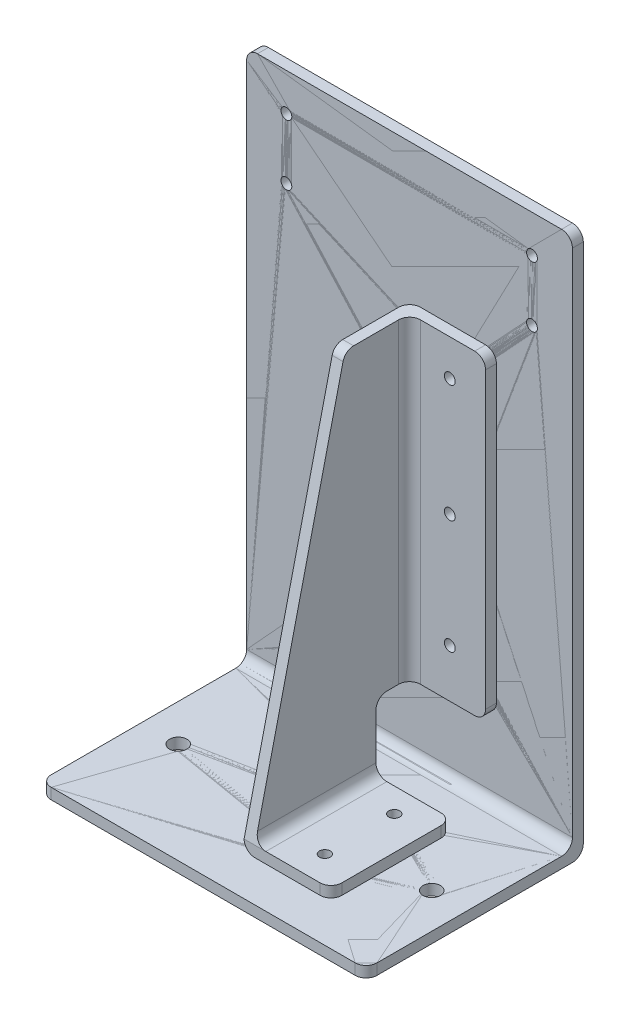
SolidWorks part; units mm, degrees
note: The reader was unsure of these and kept them because the rebuilt part matched: shared geometry of "Sketch2<3>".
ref_plane "Front Plane" through (0, 0, 0) normal (0, 0, 1) x (1, 0, 0)
ref_plane "Top Plane" through (0, 0, 0) normal (0, 1, 0) x (1, 0, 0)
ref_plane "Right Plane" through (0, 0, 0) normal (1, 0, 0) x (0, 0, -1)
sketch "Sketch1" plane through (0, 0, 0) normal (1, 0, 0) x (0, 0, -1)
  line L0 (-200, 0) -> (0, 0)
  line L1 (0, 0) -> (0, 500)
  line L2 (-200, 10) -> (-10, 10)
  line L3 (-10, 10) -> (-10, 500)
  line L4 (-200, 0) -> (-200, 10)
  line L5 (0, 500) -> (-10, 500)
  dimension "D1" = 500
  dimension "D2" = 200
  dimension "D3" = 10
extrude "Boss-Extrude1" add sketch "Sketch1" against normal blind 300 contours L1 L5 L3 L2 L4 L0
sketch "Sketch2" plane through (0, 0, 0) normal (1, 0, 0) x (0, 0, -1)
  line L0 (-10, 372.8517) -> (-79.4391, 372.8517)
  line L1 (-10, 10) -> (-10, 500) construction
  line L2 (-79.4391, 372.8517) -> (-162.346, 20)
  line L3 (-162.346, 20) -> (-162.346, 10)
  line L4 (-200, 10) -> (-10, 10) construction
  line L5 (-162.346, 10) -> (-50.9191, 10)
  line L6 (-50.9191, 10) -> (-50.9191, 82.1965)
  line L7 (-50.9191, 82.1965) -> (-10, 82.1965)
  line L8 (-10, 82.1965) -> (-10, 372.8517)
  line L9 (-162.346, 20) -> (-50.9191, 20)
  line L10 (-20, 82.1965) -> (-20, 372.8517)
  line L11 (-162.346, 10) -> (-162.346, 20)
  line L12 (-50.9191, 10) -> (-50.9191, 20)
  line L13 (-10, 82.1965) -> (-20, 82.1965)
  line L14 (-10, 372.8517) -> (-20, 372.8517)
  dimension "D1" = 10
  dimension "D2" = 10
extrude "Boss-Extrude2" add sketch "Sketch2" against normal blind 10 from offset 140 separate body contours L7 L10 L0 L2 L9 L6 offset against normal yes
extrude "Boss-Extrude3" add sketch "Sketch2<3>" along normal blind 80 from offset 150 contours L9 L3 L5 L6 | L10 L7 L8 L0 offset against normal yes
sketch "Sketch2<3>" plane through (0, 0, 0) normal (1, 0, 0) x (0, 0, -1) same geometry as "Sketch2"
fillet "Fillet1" radius 10 6 edges at (-300, 5, 200) (0, 5, 200) (-300, 500, 5) (0, 500, 5) (-150, 0, 0) (-150, 10, 10)
fillet "Fillet2" radius 10 10 edges at (-145, 82.1965, 50.9191) (-150, 10, 106.6326) (-70, 15, 50.9191) (-70, 15, 162.346) (-70, 82.1965, 15) (-140, 227.5241, 20) (-145, 372.8517, 79.4391) (-70, 372.8517, 15) (-150, 227.5241, 10) (-140, 20, 106.6326)
sketch "Sketch3" plane through (0, 0, 20) normal (0, 0, 1) x (1, 0, 0)
sketch "Sketch5" plane through (0, 0, 20) normal (0, 0, 1) x (1, 0, 0)
  point P0 (-102.9089, 339.5394)
  point P2 (-102.9089, 231.4289)
  point P4 (-102.9089, 126.6346)
  point P6 (-37.2466, 465.5579)
  point P8 (-37.2466, 409.8445)
  point P10 (-263.4166, 409.8445)
  point P12 (-263.4166, 465.5579)
hole_wizard "Ø10.0mm Dowel Hole1" positions "Sketch5" profile "Sketch4" hole size "Ø10.0" standard "ANSI Metric" end condition through all
sketch "Sketch4" plane through (-102.9089, 339.5394, 20) normal (1, 0, 0) x (0, -1, 0)
  line L0 (0, 0) -> (0, 20)
  line L1 (0, 20) -> (5, 20)
  line L2 (5, 20) -> (5, 0)
  line L5 (5, 0) -> (0, 0)
  line L11 (0, -6.35) -> (0, 107.95) construction
  dimension "Thru Hole Dia." = 10
  dimension "Thru Hole Depth" = 20
sketch "Sketch6" plane through (0, 20, 0) normal (0, 1, 0) x (1, 0, 0)
  point P0 (-100.7985, -73.2467)
  point P2 (-100.7985, -137.2086)
hole_wizard "Ø10.0mm Dowel Hole2" positions "Sketch6" profile "Sketch7" hole size "Ø10.0" standard "ANSI Metric" end condition through all
sketch "Sketch7" plane through (-100.7985, 20, 73.2467) normal (1, 0, 0) x (0, 0, 1)
  line L0 (0, 0) -> (0, 20)
  line L1 (0, 20) -> (5, 20)
  line L2 (5, 20) -> (5, 0)
  line L5 (5, 0) -> (0, 0)
  line L11 (0, -6.35) -> (0, 107.95) construction
  dimension "Thru Hole Dia." = 10
  dimension "Thru Hole Depth" = 20
sketch "Sketch8" plane through (0, 10, 0) normal (0, 1, 0) x (1, 0, 0)
  point P0 (-32.5315, -107.0727)
  point P2 (-265.931, -107.0727)
hole_wizard "Ø16.0mm Dowel Hole1" positions "Sketch8" profile "Sketch9" hole size "Ø16.0" standard "ANSI Metric" end condition through all
sketch "Sketch9" plane through (-32.5315, 10, 107.0727) normal (1, 0, 0) x (0, 0, 1)
  line L0 (0, 0) -> (0, 10)
  line L1 (0, 10) -> (8, 10)
  line L2 (8, 10) -> (8, 0)
  line L5 (8, 0) -> (0, 0)
  line L11 (0, -6.35) -> (0, 107.95) construction
  dimension "Thru Hole Dia." = 16
  dimension "Thru Hole Depth" = 10
surface "Surface-Offset1" parameters "D1"=0
split "Split1" trimming surface bodies 109 bodies to split 107 108 resulting bodies 110 111
